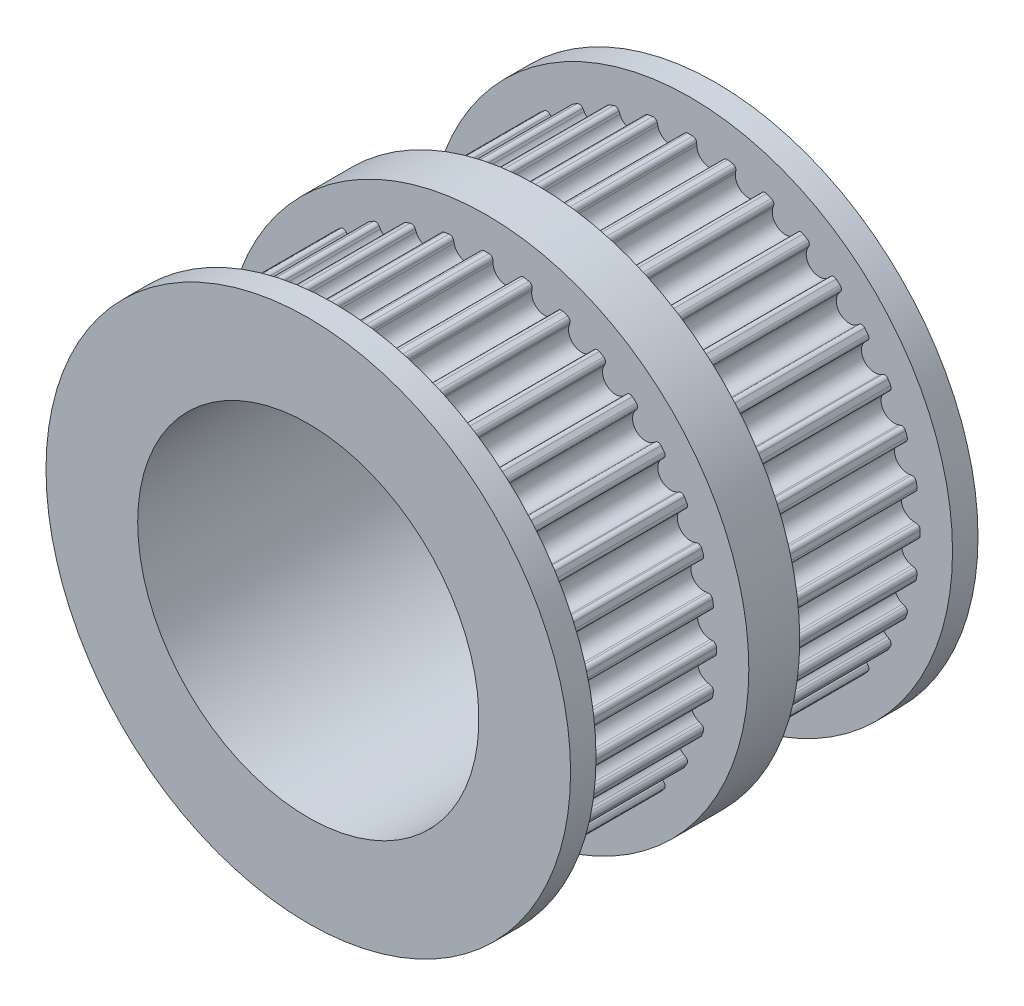
SolidWorks part; units mm, degrees
ref_plane "前视基准面" through (0, 0, 0) normal (0, 0, 1) x (1, 0, 0)
ref_plane "上视基准面" through (0, 0, 0) normal (0, 1, 0) x (1, 0, 0)
ref_plane "右视基准面" through (0, 0, 0) normal (1, 0, 0) x (0, 0, -1)
sketch "Sketch2" plane through (0, 0, 0) normal (0, 0, 1) x (1, 0, 0)
  circle A0 centre (0, 0) radius 45.15
  dimension "D1" = 90.3
extrude "Extrude1" add sketch "Sketch2" along normal blind 30
sketch "Sketch1" plane through (0, 0, 0) normal (0, 0, 1) x (1, 0, 0)
  line L0 (0, 0) -> (0, 45.835) construction
  line L1 (0, 0) -> (-3.9948, 45.6606) construction
  line L2 (-1.2656, 44.3946) -> (-1.2821, 43.9222)
  line L3 (-6.4627, 43.9399) -> (-6.3644, 43.4775)
  circle A0 centre (0, 0) radius 45.835 construction
  arc A1 (-0.4946, 45.1473) -> (-7.3526, 44.5473) centre (0, 0) ccw
  arc A2 (-6.3644, 43.4775) -> (-1.2821, 43.9222) centre (-3.8505, 44.0119) ccw
  arc A3 (-0.4946, 45.1473) -> (-1.2656, 44.3946) centre (-0.4861, 44.3673) ccw
  arc A4 (-7.3526, 44.5473) -> (-6.4627, 43.9399) centre (-7.2256, 43.7777) cw
  point P4 (45.6606, 3.9948)
  point P5 (44.2732, 11.863)
  point P6 (41.5406, 19.3707)
  point P7 (37.5458, 26.2899)
  point P8 (32.4102, 32.4102)
  point P9 (26.2899, 37.5458)
  point P10 (19.3707, 41.5406)
  point P11 (11.863, 44.2732)
  point P12 (3.9948, 45.6606)
  point P13 (-3.9948, 45.6606)
  point P14 (-11.863, 44.2732)
  point P15 (-19.3707, 41.5406)
  point P16 (-26.2899, 37.5458)
  point P17 (-32.4102, 32.4102)
  point P18 (-37.5458, 26.2899)
  point P19 (-41.5406, 19.3707)
  point P20 (-44.2732, 11.863)
  point P21 (-45.6606, 3.9948)
  point P22 (-45.6606, -3.9948)
  point P23 (-44.2732, -11.863)
  point P24 (-41.5406, -19.3707)
  point P25 (-37.5458, -26.2899)
  point P26 (-32.4102, -32.4102)
  point P27 (-26.2899, -37.5458)
  point P28 (-19.3707, -41.5406)
  point P29 (-11.863, -44.2732)
  point P30 (-3.9948, -45.6606)
  point P31 (3.9948, -45.6606)
  point P32 (11.863, -44.2732)
  point P33 (19.3707, -41.5406)
  point P34 (26.2899, -37.5458)
  point P35 (32.4102, -32.4102)
  point P36 (37.5458, -26.2899)
  point P37 (41.5406, -19.3707)
  point P38 (44.2732, -11.863)
  point P39 (45.6606, -3.9948)
  dimension "D1" = 91.67
  dimension "D2" = 90.3
  dimension "D3" = 5.14
  dimension "D4" = 3.54
  dimension "D5" = 1.56
  dimension "D6" = 7
extrude "Extrude2" cut sketch "Sketch1" along normal blind 30
pattern_circular "CirPattern1" count 36 over 360 about axis through (0, 0, 30) along (0, 0, 1) of "Extrude2"
sketch "Sketch5" plane through (0, 0, 30) normal (0, 0, 1) x (1, 0, 0)
  circle A0 centre (0, 0) radius 51.5
  dimension "D1" = 103
extrude "Extrude4" add sketch "Sketch5" along normal blind 10
ref_plane "Plane3" through (0, 0, 35) normal (0, 0, 1) x (1, 0, 0)
sketch "Sketch6" plane through (0, 0, 0) normal (0, 0, -1) x (-1, 0, 0)
  circle A0 centre (0, 0) radius 51.5
  dimension "D1" = 103
extrude "Extrude5" add sketch "Sketch6" along normal blind 5
mirror "Mirror6" about plane through (0, 0, 35) normal (0, 0, 1) of "Extrude5", "Extrude1", "Extrude2", "CirPattern1"
sketch "Sketch7" plane through (0, 0, -5) normal (0, 0, -1) x (-1, 0, 0)
  circle A0 centre (0, 0) radius 33.5
  dimension "D1" = 67
extrude "Extrude6" cut sketch "Sketch7" against normal through all
ref_plane "Plane4" through (0, 0, 15) normal (0, 0, -1) x (-1, 0, 0)
